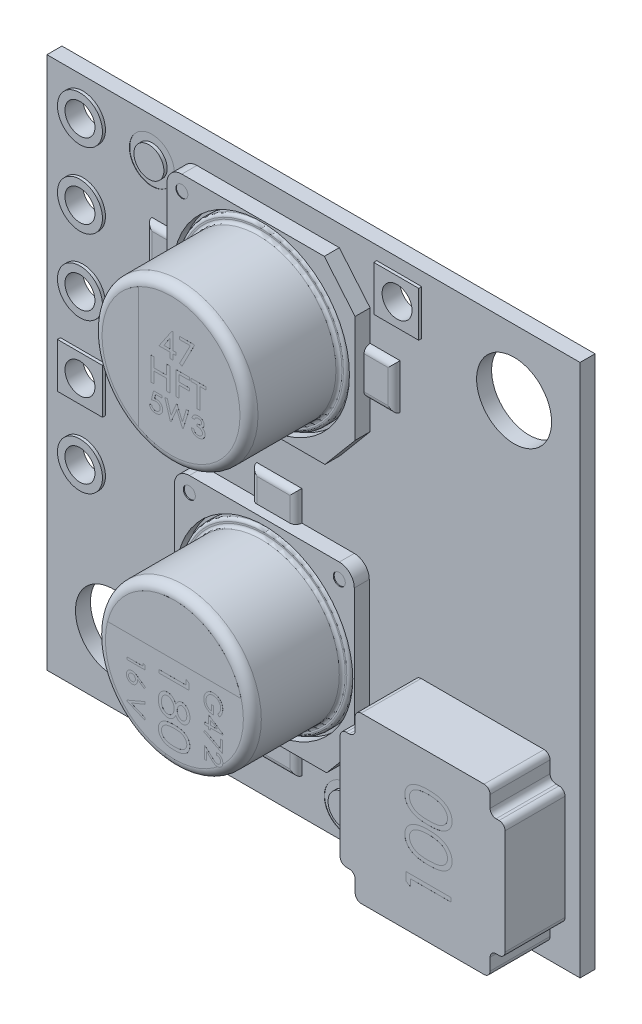
SolidWorks part; units mm, degrees
ref_plane "Alzado" through (0, 0, 0) normal (0, 0, 1) x (1, 0, 0)
ref_plane "Planta" through (0, 0, 0) normal (0, 1, 0) x (1, 0, 0)
ref_plane "Vista lateral" through (0, 0, 0) normal (1, 0, 0) x (0, 0, -1)
sketch "Croquis2" plane through (0, 0, 0) normal (0, 0, 1) x (1, 0, 0)
  line L0 (0, -55) -> (0, 55) construction
  line L1 (-8.89, 8.89) -> (8.89, 8.89)
  line L2 (-8.89, 8.89) -> (-8.89, -8.89)
  line L3 (-8.89, -8.89) -> (8.89, -8.89)
  line L4 (8.89, 8.89) -> (8.89, -8.89)
  line L5 (55, 0) -> (-55, 0) construction
  point P4 (-8.89, 0)
  point P5 (0, 8.89)
  dimension "D1" = 17.78
  dimension "D2" = 17.78
extrude "Saliente-Extruir1" add sketch "Croquis2" along normal mid plane 0.5
sketch "Croquis3" plane through (0, 0, 0.25) normal (0, 0, 1) x (1, 0, 0)
  line L0 (-7.69, 8.89) -> (-7.69, 0.69) construction
  line L1 (8.89, 8.89) -> (-8.89, 8.89) construction
  line L2 (-8.89, -8.89) -> (8.89, -8.89) construction
  line L3 (-8.89, 8.89) -> (-8.89, -8.89) construction
  line L4 (-6.94, 0.94) -> (-6.94, -0.56)
  line L5 (-6.94, -0.56) -> (-8.44, -0.56)
  line L6 (-8.44, -0.56) -> (-8.44, 0.94)
  line L7 (-8.44, 0.94) -> (-6.94, 0.94)
  line L8 (-7.69, -0.56) -> (-7.69, -8.89) construction
  line L10 (2.11, 8.44) -> (3.61, 8.44)
  line L11 (2.11, 8.44) -> (2.11, 6.94)
  line L12 (2.11, 6.94) -> (3.61, 6.94)
  line L13 (3.61, 8.44) -> (3.61, 6.94)
  circle A0 centre (-7.69, 7.69) radius 0.75
  circle A1 centre (-7.69, 5.19) radius 0.75
  circle A2 centre (-7.69, 2.69) radius 0.75
  circle A3 centre (1.11, -7.89) radius 0.5247
  circle A4 centre (-7.69, -2.31) radius 0.75
  circle A5 centre (-7.69, 7.69) radius 0.5
  circle A6 centre (-7.69, 5.19) radius 0.5
  circle A7 centre (-7.69, 2.69) radius 0.5
  circle A8 centre (-5.39, 7.59) radius 0.5
  circle A9 centre (-7.69, -2.31) radius 0.5
  dimension "D2" = 1.5
  dimension "D3" = 1.5
  dimension "D4" = 1.5
  dimension "D5" = 1.5
  dimension "D6" = 1.5
  dimension "D12" = 1
  dimension "D13" = 1
  dimension "D14" = 1
  dimension "D15" = 10
  dimension "D16" = 1
  dimension "D19" = 1
  dimension "D1" = 1.2
  dimension "D7" = 1.2
  dimension "D8" = 2.5
  dimension "D9" = 2.5
  dimension "D10" = 11
  dimension "D11" = 1
  dimension "D17" = 3.5
  dimension "D18" = 1.3
extrude "Saliente-Extruir2" add sketch "Croquis3" along normal blind 0.1
sketch "Croquis4" plane through (0, 0, 0.25) normal (0, 0, 1) x (1, 0, 0)
  circle A0 centre (-7.69, 7.69) radius 0.5
  circle A1 centre (-7.69, 5.19) radius 0.5
  circle A2 centre (-7.69, 2.69) radius 0.5
  circle A3 centre (-7.69, -2.31) radius 0.5
  circle A4 centre (2.8872, 7.69) radius 0.5
  circle A5 centre (-7.69, 0.19) radius 0.5
  dimension "D1" = 1
  dimension "D2" = 1
extrude "Cortar-Extruir1" cut sketch "Croquis4" against normal blind 21.5 and the other way blind 19
sketch "Croquis5" plane through (0, 0, 0.25) normal (0, 0, 1) x (1, 0, 0)
  circle A0 centre (1.11, -7.89) radius 0.5247
  circle A1 centre (1.11, -7.89) radius 0.75
  dimension "D1" = 1.5
extrude "Cortar-Extruir2" cut sketch "Croquis5" against normal blind 0.01
sketch "Croquis6" plane through (0, 0, 0.25) normal (0, 0, 1) x (1, 0, 0)
  circle A0 centre (-5.39, 7.59) radius 0.5
  circle A1 centre (-5.39, 7.59) radius 0.75
  dimension "D1" = 1.5
extrude "Cortar-Extruir3" cut sketch "Croquis6" against normal blind 0.01
sketch "Croquis7" plane through (0, 0, 0.25) normal (0, 0, 1) x (1, 0, 0)
  line L0 (-8.89, -8.89) -> (8.89, -8.89) construction
  line L1 (-8.89, 8.89) -> (-8.89, -8.89) construction
  line L2 (8.89, -8.89) -> (8.89, 8.89) construction
  line L3 (8.89, 8.89) -> (-8.89, 8.89) construction
  circle A0 centre (-6.69, -6.69) radius 1.25
  circle A1 centre (6.69, 6.69) radius 1.25
  dimension "D1" = 2.5
  dimension "D2" = 2.5
  dimension "D3" = 2.2
  dimension "D4" = 2.2
  dimension "D5" = 2.2
  dimension "D6" = 2.2
extrude "Cortar-Extruir4" cut sketch "Croquis7" against normal blind 30.01
sketch "Croquis8" plane through (0, 0, 0.25) normal (0, 0, 1) x (1, 0, 0)
  line L0 (-8.89, -8.89) -> (8.89, -8.89) construction
  line L1 (-5.39, 5.94) -> (-4.39, 5.94)
  line L2 (-5.39, 5.94) -> (-5.39, 4.44)
  line L3 (-5.39, 4.44) -> (-4.39, 4.44)
  line L4 (2.8872, 5.94) -> (2.8872, 4.44)
  line L5 (-1.89, 0.61) -> (-0.39, 0.61)
  line L6 (-1.89, 0.61) -> (-1.89, -0.39)
  line L7 (-1.89, -7.69) -> (-0.39, -7.69)
  line L8 (-0.39, 0.61) -> (-0.39, -0.39)
  line L9 (-8.89, 8.89) -> (-8.89, -8.89) construction
  line L10 (-4.39, 4.44) -> (-4.39, 5.94)
  line L11 (-1.89, -6.69) -> (-0.39, -6.69)
  line L12 (1.8872, 5.94) -> (1.8872, 4.44)
  line L13 (1.8872, 5.94) -> (2.8872, 5.94)
  line L14 (1.8872, 4.44) -> (2.8872, 4.44)
  line L15 (-1.89, -0.39) -> (-0.39, -0.39)
  line L16 (-1.89, -6.69) -> (-1.89, -7.69)
  line L18 (-0.39, -6.69) -> (-0.39, -7.69)
  dimension "D1" = 1.5
  dimension "D2" = 8.2772
  dimension "D3" = 1.5
  dimension "D4" = 8.3
  dimension "D5" = 7
  dimension "D6" = 1.2
  dimension "D7" = 1
  dimension "D8" = 1
  dimension "D9" = 1
  dimension "D10" = 1
extrude "Saliente-Extruir3" add sketch "Croquis8" along normal blind 0.2
fillet "Redondeo3" radius 0.2 3 edges at (-5.39, 5.19, 0.45) (-4.89, 4.44, 0.45) (-4.89, 5.94, 0.45) type face fillet first side face at (-4.89, 5.19, 0.45) second side face at (-4.89, 5.94, 0.35) second side face at (-5.39, 5.19, 0.35) second side face at (-4.89, 4.44, 0.35)
fillet "Redondeo4" radius 0.2 3 edges at (2.3872, 4.44, 0.45) (2.8872, 5.19, 0.45) (2.3872, 5.94, 0.45) type face fillet first side face at (2.3872, 5.19, 0.45) second side face at (2.3872, 4.44, 0.35) second side face at (2.8872, 5.19, 0.35) second side face at (2.3872, 5.94, 0.35)
sketch "Croquis12" plane through (0, 0, 0.25) normal (0, 0, 1) x (1, 0, 0)
  line L0 (-5.19, 5.19) -> (-2.7163, 5.19) construction
  line L1 (-3.89, 2.19) -> (0.8826, 2.19)
  line L2 (-4.39, 2.69) -> (-4.39, 7.69)
  line L3 (-3.89, 8.19) -> (0.86, 8.19)
  line L4 (1.8872, 3.9301) -> (1.8872, 6.9659)
  line L5 (-5.19, 5.74) -> (-5.19, 4.64) construction
  line L6 (0.86, 8.19) -> (1.8721, 6.9838)
  line L7 (0.8826, 2.19) -> (1.8721, 3.3692)
  line L8 (8.89, 8.89) -> (-8.89, 8.89) construction
  line L9 (-8.89, -8.89) -> (8.89, -8.89) construction
  line L10 (1.8872, 3.9301) -> (1.8872, 3.3872)
  line L11 (1.8721, 3.3692) -> (1.8872, 3.3872)
  line L12 (1.8721, 6.9838) -> (1.8872, 6.9659)
  arc A0 (-3.89, 2.19) -> (-4.39, 2.69) centre (-3.89, 2.69) cw
  arc A1 (-4.39, 7.69) -> (-3.89, 8.19) centre (-3.89, 7.69) cw
  point P4 (-4.39, 5.19)
  point P11 (-4.39, 2.19)
  point P14 (-4.39, 8.19)
  dimension "D2" = 0.5
  dimension "D1" = 6
  dimension "D3" = 50
  dimension "D4" = 50
  dimension "D5" = 4.75
extrude "Saliente-Extruir4" add sketch "Croquis12" along normal blind 0.5
sketch "Croquis13" plane through (0, 0, 0.75) normal (0, 0, 1) x (1, 0, 0)
  line L0 (-4.39, 5.19) -> (1.8872, 5.19) construction
  line L1 (-4.39, 4.64) -> (-4.39, 5.74) construction
  line L2 (1.8872, 5.74) -> (1.8872, 4.64) construction
  circle A0 centre (-1.2514, 5.19) radius 2.95
  point P6 (-1.2514, 5.19)
  dimension "D2" = 5.9
  dimension "D1" = 6.2772
extrude "Cortar-Extruir11" cut sketch "Croquis13" against normal blind 0.3
sketch "Croquis14" plane through (0, 0, 0.45) normal (0, 0, 1) x (1, 0, 0)
  circle A0 centre (-1.2514, 5.19) radius 2.85
  dimension "D1" = 5.7
extrude "Saliente-Extruir5" add sketch "Croquis14" along normal blind 0.3
sketch "Croquis15" plane through (0, 0, 0.75) normal (0, 0, 1) x (1, 0, 0)
  circle A0 centre (-1.2514, 5.19) radius 2.6
  dimension "D1" = 5.2
extrude "Saliente-Extruir6" add sketch "Croquis15" along normal blind 3
fillet "Redondeo5" radius 0.3 1 edges at (1.3486, 5.19, 3.75) type face fillet first side face at (1.3486, 5.19, 3.75) second side face at (1.3486, 5.19, 3.75)
fillet "Redondeo6" radius 0.1 1 edges at (1.5986, 5.19, 0.75) type face fillet first side face at (1.3486, 5.19, 0.75) second side face at (1.5986, 5.19, 0.75)
fillet "Redondeo7" radius 0.1 1 edges at (1.3486, 5.19, 0.75) type face fillet first side face at (1.4986, 5.19, 0.75) second side face at (1.3486, 5.19, 3.45)
sketch "Croquis16" plane through (0, 0, 0.75) normal (0, 0, 1) x (1, 0, 0)
  circle A0 centre (-3.89, 7.69) radius 0.2
  circle A1 centre (-3.89, 2.69) radius 0.2
  dimension "D1" = 0.4
  dimension "D2" = 0.4
extrude "Cortar-Extruir12" cut sketch "Croquis16" against normal blind 0.02
sketch "Croquis17" plane through (0, 0, 3.75) normal (0, 0, 1) x (1, 0, 0)
  line L0 (-2.3393, 7.2165) -> (-2.3393, 3.1635)
  arc A0 (-2.3393, 7.2165) -> (-2.3393, 3.1635) centre (-1.2514, 5.19) ccw
extrude "Saliente-Extruir7" add sketch "Croquis17" along normal blind 0.001
sketch "Croquis18" plane through (0, 0, 3.75) normal (0, 0, 1) x (1, 0, 0)
  line L0 (-2.3514, 5.6666) -> (0.2353, 5.6666) construction
  line L1 (-2.3393, 4.6677) -> (0.2353, 4.6677) construction
  line L2 (-2.3393, 3.1635) -> (-2.3393, 7.2165) construction
  line L3 (-2.3393, 3.861) -> (0.2353, 3.861) construction
  arc A0 (-2.3393, 7.2165) -> (-2.3393, 3.1635) centre (-1.2514, 5.19) ccw construction
  text T0 "47" font "Century Gothic" height 0.8
  text T1 "HFT" font "Century Gothic" height 0.78
  text T2 "5W3" font "Century Gothic" height 0.6
  point P3 (-3.5514, 5.19)
  dimension "D1" = 1.2
extrude "Saliente-Extruir9" add sketch "Croquis18" along normal blind 0.001 separate body
fillet "Redondeo8" radius 0.2 3 edges at (-1.89, 0.11, 0.45) (-0.39, 0.11, 0.45) (-1.14, 0.61, 0.45) type face fillet first side face at (-1.14, 0.11, 0.45) second side face at (-1.14, 0.61, 0.35) second side face at (-0.39, 0.11, 0.35) second side face at (-1.89, 0.11, 0.35)
fillet "Redondeo9" radius 0.2 3 edges at (-0.39, -7.19, 0.45) (-1.89, -7.19, 0.45) (-1.14, -7.69, 0.45) type face fillet first side face at (-1.14, -7.19, 0.45) second side face at (-1.89, -7.19, 0.35) second side face at (-1.14, -7.69, 0.35) second side face at (-0.39, -7.19, 0.35)
sketch "Croquis19" plane through (0, 0, 0.25) normal (0, 0, 1) x (1, 0, 0)
  line L0 (-3.64, -0.39) -> (1.36, -0.39)
  line L1 (1.86, -0.89) -> (1.86, -5.59)
  line L2 (-4.14, -0.89) -> (-4.14, -5.1804)
  line L3 (0.1105, -6.69) -> (-2.8733, -6.69)
  line L4 (-4.14, -5.1804) -> (-2.938, -6.6129)
  line L5 (1.0017, -6.6129) -> (1.86, -5.59)
  line L6 (-8.89, -8.89) -> (8.89, -8.89) construction
  line L7 (0.1105, -6.69) -> (0.937, -6.69)
  line L8 (1.0017, -6.6129) -> (0.937, -6.69)
  line L9 (-2.938, -6.6129) -> (-2.8733, -6.69)
  line L10 (-1.14, 0.61) -> (-1.14, -8.1637) construction
  line L11 (-0.39, 0.61) -> (-1.89, 0.61) construction
  arc A0 (1.36, -0.39) -> (1.86, -0.89) centre (1.36, -0.89) cw
  arc A1 (-3.64, -0.39) -> (-4.14, -0.89) centre (-3.64, -0.89) ccw
  point P17 (-1.14, -0.39)
  dimension "D1" = 0.5
  dimension "D2" = 50
  dimension "D3" = 50
  dimension "D4" = 6
  dimension "D5" = 4.7
extrude "Saliente-Extruir10" add sketch "Croquis19" along normal blind 0.5
sketch "Croquis20" plane through (0, 0, 0.75) normal (0, 0, 1) x (1, 0, 0)
  line L0 (-1.14, -0.39) -> (-1.14, -6.69) construction
  line L1 (1.36, -0.39) -> (-3.64, -0.39) construction
  line L2 (-0.59, -6.69) -> (-1.69, -6.69) construction
  circle A0 centre (-1.14, -3.54) radius 2.95
  dimension "D1" = 5.9
extrude "Cortar-Extruir13" cut sketch "Croquis20" against normal blind 0.3
sketch "Croquis21" plane through (0, 0, 0.45) normal (0, 0, 1) x (1, 0, 0)
  circle A0 centre (-1.14, -3.54) radius 2.85
  dimension "D1" = 5.7
extrude "Saliente-Extruir11" add sketch "Croquis21" along normal blind 0.3
sketch "Croquis22" plane through (0, 0, 0.75) normal (0, 0, 1) x (1, 0, 0)
  circle A0 centre (-1.14, -3.54) radius 2.6
  dimension "D1" = 5.2
extrude "Saliente-Extruir12" add sketch "Croquis22" along normal blind 3
fillet "Redondeo10" radius 0.3 1 edges at (1.46, -3.54, 3.75) type face fillet first side face at (1.46, -3.54, 3.75) second side face at (1.46, -3.54, 3.75)
fillet "Redondeo11" radius 0.1 1 edges at (1.71, -3.54, 0.75) type face fillet first side face at (1.71, -3.54, 0.75) second side face at (1.46, -3.54, 0.75)
fillet "Redondeo12" radius 0.1 1 edges at (1.46, -3.54, 0.75) type face fillet first side face at (1.61, -3.54, 0.75) second side face at (1.46, -3.54, 3.45)
sketch "Croquis23" plane through (0, 0, 0.75) normal (0, 0, 1) x (1, 0, 0)
  circle A0 centre (-3.64, -0.89) radius 0.2
  circle A1 centre (1.36, -0.89) radius 0.2
  dimension "D1" = 0.4
  dimension "D2" = 0.4
extrude "Cortar-Extruir14" cut sketch "Croquis23" against normal blind 0.03
sketch "Croquis24" plane through (0, 0, 3.75) normal (0, 0, 1) x (1, 0, 0)
  line L0 (-3.3686, -2.9715) -> (1.0886, -2.9715)
  arc A0 (1.0886, -2.9715) -> (-3.3686, -2.9715) centre (-1.14, -3.54) ccw
extrude "Saliente-Extruir13" add sketch "Croquis24" along normal blind 0.001
sketch "Croquis25" plane through (0, 0, 3.75) normal (0, 0, 1) x (1, 0, 0)
  line L0 (-0.14, -2.9715) -> (-0.14, -5.6112) construction
  line L1 (-3.3686, -2.9715) -> (1.0886, -2.9715) construction
  line L2 (-4.14, -0.89) -> (-4.14, -5.1804) construction
  line L3 (-1.6476, -2.9715) -> (-1.6476, -5.7833) construction
  line L4 (-3.3686, -2.9715) -> (1.0886, -2.9715) construction
  line L5 (-2.7232, -2.9715) -> (-2.7232, -5.2084) construction
  arc A0 (-3.3686, -2.9715) -> (1.0886, -2.9715) centre (-1.14, -3.54) ccw construction
  text T0 "G472" font "Century Gothic" height 0.6
  text T1 "180" font "Century Gothic" height 1
  text T2 "16 V" font "Century Gothic" height 0.6
  dimension "D1" = 4
extrude "Saliente-Extruir14" add sketch "Croquis25" along normal blind 0.001 separate body
sketch "Croquis26" plane through (0, 0, 0.25) normal (0, 0, 1) x (1, 0, 0)
  line L0 (8.89, -8.89) -> (8.89, 8.89) construction
  line L1 (3.59, -2.89) -> (7.69, -2.89)
  line L2 (2.89, -3.89) -> (2.89, -7.39)
  line L3 (3.59, -8.39) -> (7.69, -8.39)
  line L4 (8.39, -3.89) -> (8.39, -7.39)
  line L5 (-8.89, -8.89) -> (8.89, -8.89) construction
  line L6 (3.09, -3.69) -> (3.19, -3.69)
  line L7 (3.09, -7.59) -> (3.19, -7.59)
  line L8 (3.39, -3.09) -> (3.39, -3.49)
  line L9 (7.89, -3.09) -> (7.89, -3.49)
  line L10 (3.39, -7.79) -> (3.39, -8.19)
  line L11 (8.09, -3.69) -> (8.19, -3.69)
  line L12 (7.89, -7.79) -> (7.89, -8.19)
  line L13 (8.09, -7.59) -> (8.19, -7.59)
  arc A0 (8.19, -7.59) -> (8.39, -7.39) centre (8.19, -7.39) ccw
  arc A1 (7.89, -8.19) -> (7.69, -8.39) centre (7.69, -8.19) cw
  arc A2 (3.39, -8.19) -> (3.59, -8.39) centre (3.59, -8.19) ccw
  arc A3 (3.09, -7.59) -> (2.89, -7.39) centre (3.09, -7.39) cw
  arc A4 (8.19, -3.69) -> (8.39, -3.89) centre (8.19, -3.89) cw
  arc A5 (7.89, -3.09) -> (7.69, -2.89) centre (7.69, -3.09) ccw
  arc A6 (3.09, -3.69) -> (2.89, -3.89) centre (3.09, -3.89) ccw
  arc A7 (3.39, -3.09) -> (3.59, -2.89) centre (3.59, -3.09) cw
  arc A8 (7.89, -7.79) -> (8.09, -7.59) centre (8.09, -7.79) cw
  arc A9 (3.39, -7.79) -> (3.19, -7.59) centre (3.19, -7.79) ccw
  arc A10 (8.09, -3.69) -> (7.89, -3.49) centre (8.09, -3.49) cw
  arc A11 (3.39, -3.49) -> (3.19, -3.69) centre (3.19, -3.49) cw
  point P34 (7.89, -7.59)
  dimension "D9" = 0.2
  dimension "D1" = 0.5
  dimension "D2" = 0.5
  dimension "D3" = 0.5
  dimension "D4" = 0.5
  dimension "D5" = 0.8
  dimension "D6" = 0.8
  dimension "D7" = 5.5
  dimension "D8" = 5.5
extrude "Saliente-Extruir15" add sketch "Croquis26" along normal blind 2
sketch "Croquis27" plane through (0, 0, 2.25) normal (0, 0, 1) x (1, 0, 0)
  line L0 (6.5838, -2.89) -> (6.5838, -8.39) construction
  line L1 (7.69, -2.89) -> (3.59, -2.89) construction
  line L2 (3.59, -8.39) -> (7.69, -8.39) construction
  text T0 "100" font "Century Gothic" height 1.5
extrude "Cortar-Extruir15" cut sketch "Croquis27" against normal blind 0.001
